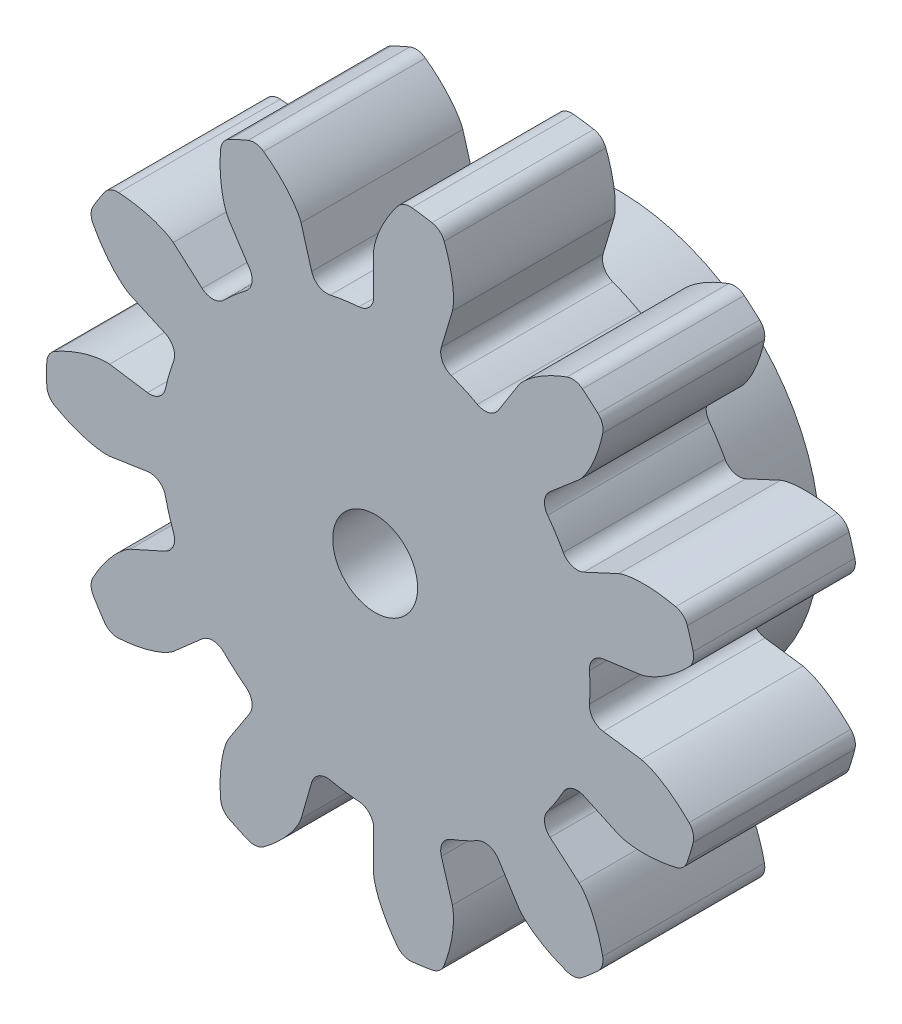
SolidWorks part; units mm, degrees
material "Brass"
ref_plane "Front Plane" through (0, 0, 0) normal (0, 0, 1) x (1, 0, 0)
ref_plane "Top Plane" through (0, 0, 0) normal (0, 1, 0) x (1, 0, 0)
ref_plane "Right Plane" through (0, 0, 0) normal (1, 0, 0) x (0, 0, -1)
sketch "Sketch1" plane through (0, 0, 0) normal (0, 0, 1) x (1, 0, 0)
  circle A0 centre (0, 0) radius 8.125
  dimension "D1" = 16.25
extrude "Boss-Extrude1" add sketch "Sketch1" along normal blind 4
sketch "Sketch2" plane through (0, 0, 4) normal (0, 0, 1) x (1, 0, 0)
  line L0 (6.5788, 0.9046) -> (0, 0) construction
  line L1 (0, 0) -> (6.5788, -0.9046) construction
  line L2 (5.263, 0.7237) -> (6.5788, 0.9046)
  line L3 (5.263, -0.7237) -> (6.5788, -0.9046)
  circle A0 centre (0, 0) radius 8.125 construction
  circle A1 centre (0, 0) radius 6.6407 construction
  circle A2 centre (0, 0) radius 6.875 construction
  circle A3 centre (0, 0) radius 5.3125 construction
  arc A4 (7.9155, 1.833) -> (7.9155, -1.833) centre (3.6281, 0) cw
  arc A5 (5.263, -0.7237) -> (5.263, 0.7237) centre (0, 0) ccw
  spline S0 degree 4 poles (6.5788, 0.9046) (6.5812, 0.905) (6.588, 0.9061) (6.6007, 0.9088) (6.6213, 0.9136) (6.6473, 0.9207) (6.6807, 0.931) (6.7198, 0.9444) (6.7623, 0.9605) (6.8082, 0.9795) (6.8535, 0.9997) (6.8984, 1.0212) (6.9427, 1.0436) (6.9959, 1.072) (7.059, 1.1079) (7.1318, 1.1523) (7.2131, 1.2057) (7.2946, 1.2633) (7.3736, 1.3225) (7.452, 1.3852) (7.5268, 1.448) (7.603, 1.5161) (7.6725, 1.5804) (7.7486, 1.6556) (7.8095, 1.7173) (7.8878, 1.8019) (7.9335, 1.8529) (7.9862, 1.9136) (8.0093, 1.9412) (8.0235, 1.9582) knots 0 0 0 0 0 0.005377 0.015084 0.028532 0.04661 0.064855 0.092111 0.119476 0.146842 0.174209 0.201575 0.228941 0.256307 0.307035 0.361767 0.4165 0.471232 0.525964 0.580697 0.635429 0.690161 0.744894 0.799626 0.854358 0.909091 0.954545 1 1 1 1 1 construction
  spline S1 degree 4 poles (6.5788, 0.9046) (6.5812, 0.905) (6.588, 0.9061) (6.6007, 0.9088) (6.6213, 0.9136) (6.6473, 0.9207) (6.6807, 0.931) (6.7198, 0.9444) (6.7623, 0.9605) (6.8082, 0.9795) (6.8535, 0.9997) (6.8984, 1.0212) (6.9427, 1.0436) (6.9959, 1.072) (7.059, 1.1079) (7.1318, 1.1523) (7.2131, 1.2057) (7.2946, 1.2633) (7.3736, 1.3225) (7.452, 1.3852) (7.5268, 1.448) (7.603, 1.5161) (7.6725, 1.5804) (7.7486, 1.6556) (7.8095, 1.7173) (7.8709, 1.7836) (7.9005, 1.8162) (7.9155, 1.833) knots 0 0 0 0 0 0.005377 0.015084 0.028532 0.04661 0.064855 0.092111 0.119476 0.146842 0.174209 0.201575 0.228941 0.256307 0.307035 0.361767 0.4165 0.471232 0.525964 0.580697 0.635429 0.690161 0.744894 0.799626 0.854358 0.909091 0.909091 0.909091 0.909091 0.909091
  spline S2 degree 4 poles (6.5788, -0.9046) (6.5812, -0.905) (6.588, -0.9061) (6.6007, -0.9088) (6.6213, -0.9136) (6.6473, -0.9207) (6.6807, -0.931) (6.7198, -0.9444) (6.7623, -0.9605) (6.8082, -0.9795) (6.8535, -0.9997) (6.8984, -1.0212) (6.9427, -1.0436) (6.9959, -1.072) (7.059, -1.1079) (7.1318, -1.1523) (7.2131, -1.2057) (7.2946, -1.2633) (7.3736, -1.3225) (7.452, -1.3852) (7.5268, -1.448) (7.603, -1.5161) (7.6725, -1.5804) (7.7486, -1.6556) (7.8095, -1.7173) (7.8878, -1.8019) (7.9335, -1.8529) (7.9862, -1.9136) (8.0093, -1.9412) (8.0235, -1.9582) knots 0 0 0 0 0 0.005377 0.015084 0.028532 0.04661 0.064855 0.092111 0.119476 0.146842 0.174209 0.201575 0.228941 0.256307 0.307035 0.361767 0.4165 0.471232 0.525964 0.580697 0.635429 0.690161 0.744894 0.799626 0.854358 0.909091 0.954545 1 1 1 1 1 construction
  spline S3 degree 4 poles (6.5788, -0.9046) (6.5812, -0.905) (6.588, -0.9061) (6.6007, -0.9088) (6.6213, -0.9136) (6.6473, -0.9207) (6.6807, -0.931) (6.7198, -0.9444) (6.7623, -0.9605) (6.8082, -0.9795) (6.8535, -0.9997) (6.8984, -1.0212) (6.9427, -1.0436) (6.9959, -1.072) (7.059, -1.1079) (7.1318, -1.1523) (7.2131, -1.2057) (7.2946, -1.2633) (7.3736, -1.3225) (7.452, -1.3852) (7.5268, -1.448) (7.603, -1.5161) (7.6725, -1.5804) (7.7486, -1.6556) (7.8095, -1.7173) (7.8709, -1.7836) (7.9005, -1.8162) (7.9155, -1.833) knots 0 0 0 0 0 0.005377 0.015084 0.028532 0.04661 0.064855 0.092111 0.119476 0.146842 0.174209 0.201575 0.228941 0.256307 0.307035 0.361767 0.4165 0.471232 0.525964 0.580697 0.635429 0.690161 0.744894 0.799626 0.854358 0.909091 0.909091 0.909091 0.909091 0.909091
  circle M4 centre (0, 0) radius 8.125
  dimension "D1" = 16.25
  dimension "D2" = 10.625
  dimension "D3" = 13.75
  dimension "D4" = 13.2815
extrude "Cut-Extrude1" cut sketch "Sketch2" against normal through all contours L3 S3 S1 L2 A5 M4 region at (6.9095, 0, 4)
sketch "Mate" plane through (0, 0, 0) normal (0, 0, 1) x (1, 0, 0)
  circle A0 centre (0, 0) radius 6.875
  circle A1 centre (0, 0) radius 6.875 construction
fillet "Fillet1" radius 0.3934 4 edges at (5.263, -0.7237, 2) (5.263, 0.7237, 2) (7.9155, -1.833, 2) (7.9155, 1.833, 2)
pattern_circular "CirPattern1" count 11 over 360 about axis through (0, 0, 0) along (0, 0, 1) of "Cut-Extrude1", "Fillet1"
sketch "Sketch4" plane through (0, 0, 0) normal (0, 0, 1) x (1, 0, 0)
  circle A0 centre (0, 0) radius 5
  dimension "D1" = 10
extrude "Boss-Extrude2" add sketch "Sketch4" against normal blind 2
sketch "Sketch3" plane through (0, 0, 0) normal (0, 0, 1) x (1, 0, 0)
  circle A0 centre (0, 0) radius 2.65
  dimension "D1" = 5.3
extrude "Cut-Extrude2" cut sketch "Sketch3" along normal blind 2 and the other way blind 2
sketch "Sketch5" plane through (0, 0, 0) normal (0, 0, 1) x (1, 0, 0)
  circle A0 centre (0, 0) radius 1.05
  dimension "D1" = 2.1
extrude "Cut-Extrude3" cut sketch "Sketch5" along normal through all
equation "\"DiametralPitch\"= 0.8"
equation "\"NumTeeth\"= 11"
equation "\"Addendum\"= 1 / \"DiametralPitch\""
equation "\"Dedendum\"= 1.25 / \"DiametralPitch\""
equation "\"WorkingDepth\"= 2 / \"DiametralPitch\""
equation "\"WholeDepth\"= 2.25 / \"DiametralPitch\""
equation "\"Clearance\"= 0.25 / \"DiametralPitch\""
equation "\"ToothThickness\"= 1.5708 / \"DiametralPitch\""
equation "\"CircularPitch\"= pi / \"DiametralPitch\""
equation "\"PitchCircle\"= \"NumTeeth\" / \"DiametralPitch\""
equation "\"OutsideDiameter\"= ( \"NumTeeth\" + 2 ) / \"DiametralPitch\""
equation "\"AddendumCircle\"= \"PitchCircle\" + ( 2 * \"Addendum\" )"
equation "\"DedendumCircle\"= \"PitchCircle\" - ( 2 * \"Dedendum\" )"
equation "\"PitchAngle\"= 360deg / \"NumTeeth\""
equation "\"PressureAngle\"= 15deg"
equation "\"Width\"= 4mm"
equation "\"Fillet\"= \"Clearance\" * cos ( \"PressureAngle\" ) * tan ( ( 90 + \"PressureAngle\" ) / 2 )"
equation "\"BaseCircle\"= \"PitchCircle\" * cos ( \"PressureAngle\" )"
equation "\"Alpha\"= sqr ( \"PitchCircle\" ^ 2 - \"BaseCircle\" ^ 2 ) / \"BaseCircle\" * 180 / PI - \"PressureAngle\""
equation "\"Beta\"= ( \"PitchAngle\" / 4 - \"Alpha\" )"
equation "\"Phi\"= sqr ( ( \"AddendumCircle\" / 2 ) ^ 2 - ( \"BaseCircle\" / 2 ) ^ 2 ) / ( \"BaseCircle\" / 2 )"
equation "\"D1@Sketch1\"=\"OutsideDiameter\""
equation "\"D1@Boss-Extrude1\"=\"Width\""
equation "\"D1@Sketch2\"=\"OutsideDiameter\""
equation "\"D2@Sketch2\"=\"DedendumCircle\""
equation "\"D3@Sketch2\"=\"PitchCircle\""
equation "\"D4@Sketch2\"=\"BaseCircle\""
equation "\"D1@Fillet1\"=\"Fillet\""
equation "\"D1@CirPattern1\"=\"NumTeeth\""
